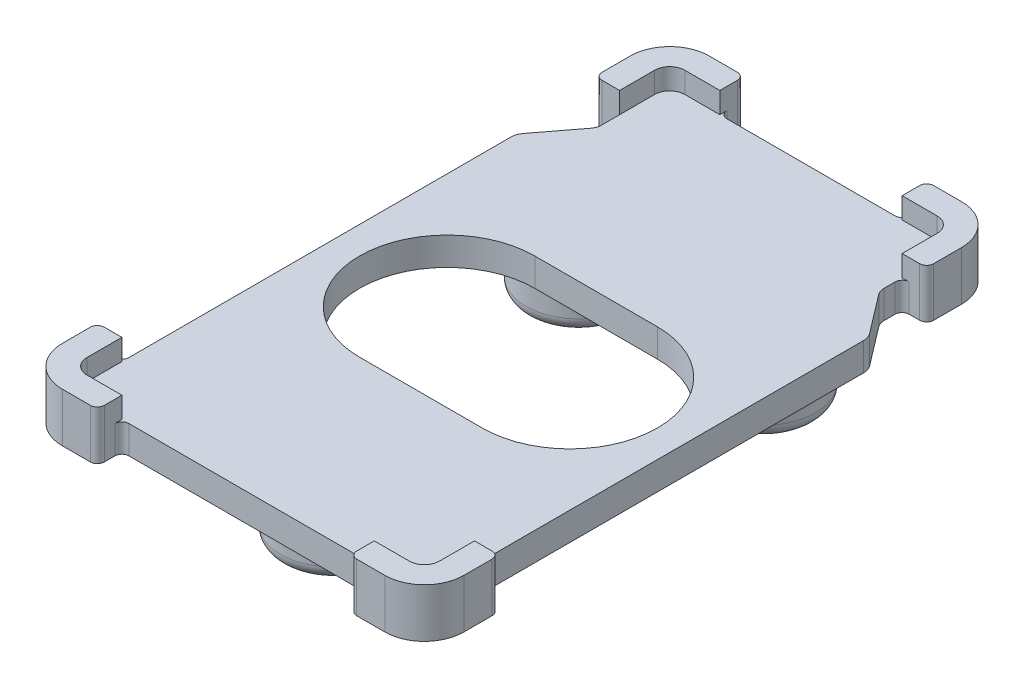
SolidWorks part; units mm, degrees
ref_plane "Alzado" through (0, 0, 0) normal (0, 0, 1) x (1, 0, 0)
ref_plane "Planta" through (0, 0, 0) normal (0, 1, 0) x (1, 0, 0)
ref_plane "Vista lateral" through (0, 0, 0) normal (1, 0, 0) x (0, 0, -1)
sketch "Croquis1" plane through (0, 0, 0) normal (0, 1, 0) x (1, 0, 0)
  line L0 (6, 80) -> (-6, 80) construction
  line L1 (6, 0) -> (-6, 0) construction
  line L2 (18, 80) -> (6, 80) construction
  line L3 (0, 80) -> (0, 0) construction
  line L4 (6, 0) -> (23, 0) construction
  line L5 (25, 2) -> (25, 62.5) construction
  line L6 (24.5908, 63.7121) -> (20.4092, 69.2003) construction
  line L7 (20, 70.4124) -> (20, 78) construction
  line L8 (-6, 0) -> (-23, 0) construction
  line L9 (-25, 2) -> (-25, 62.5) construction
  line L10 (-24.5908, 63.7121) -> (-20.4092, 69.2003) construction
  line L11 (-20, 70.4124) -> (-20, 78) construction
  line L12 (-18, 80) -> (-6, 80) construction
  line L13 (6, 80.15) -> (-6, 80.15)
  line L14 (-18, 80.15) -> (-6, 80.15)
  line L15 (-20.15, 70.4124) -> (-20.15, 78)
  line L16 (-24.7102, 63.803) -> (-20.5285, 69.2912)
  line L17 (-25.15, 2) -> (-25.15, 62.5)
  line L18 (-6, -0.15) -> (-23, -0.15)
  line L19 (6, -0.15) -> (-6, -0.15)
  line L20 (6, -0.15) -> (23, -0.15)
  line L21 (25.15, 2) -> (25.15, 62.5)
  line L22 (24.7102, 63.803) -> (20.5285, 69.2912)
  line L23 (20.15, 70.4124) -> (20.15, 78)
  line L24 (18, 80.15) -> (6, 80.15)
  arc A0 (23, 0) -> (25, 2) centre (23, 2) ccw construction
  arc A1 (25, 62.5) -> (24.5908, 63.7121) centre (23, 62.5) ccw construction
  arc A2 (20, 70.4124) -> (20.4092, 69.2003) centre (22, 70.4124) ccw construction
  arc A3 (20, 78) -> (18, 80) centre (18, 78) ccw construction
  arc A4 (-23, 0) -> (-25, 2) centre (-23, 2) cw construction
  arc A5 (-25, 62.5) -> (-24.5908, 63.7121) centre (-23, 62.5) cw construction
  arc A6 (-20, 70.4124) -> (-20.4092, 69.2003) centre (-22, 70.4124) cw construction
  arc A7 (-20, 78) -> (-18, 80) centre (-18, 78) cw construction
  arc A8 (-20.15, 78) -> (-18, 80.15) centre (-18, 78) cw
  arc A9 (-20.15, 70.4124) -> (-20.5285, 69.2912) centre (-22, 70.4124) cw
  arc A10 (-25.15, 62.5) -> (-24.7102, 63.803) centre (-23, 62.5) cw
  arc A11 (-23, -0.15) -> (-25.15, 2) centre (-23, 2) cw
  arc A12 (23, -0.15) -> (25.15, 2) centre (23, 2) ccw
  arc A13 (25.15, 62.5) -> (24.7102, 63.803) centre (23, 62.5) ccw
  arc A14 (20.15, 70.4124) -> (20.5285, 69.2912) centre (22, 70.4124) ccw
  arc A15 (20.15, 78) -> (18, 80.15) centre (18, 78) ccw
  dimension "D1" = 0.15
sketch "Croquis2" plane through (0, 0, 0) normal (0, 1, 0) x (1, 0, 0)
  line L0 (-24.7102, 63.803) -> (-20.5285, 69.2912) construction
  line L1 (-25.15, 2) -> (-25.15, 62.5) construction
  line L2 (-6, -0.15) -> (-23, -0.15) construction
  line L3 (6, -0.15) -> (-6, -0.15) construction
  line L4 (6, -0.15) -> (23, -0.15) construction
  line L5 (25.15, 2) -> (25.15, 62.5) construction
  line L6 (24.7102, 63.803) -> (20.5285, 69.2912) construction
  line L7 (20.15, 70.4124) -> (20.15, 78) construction
  line L8 (18, 80.15) -> (6, 80.15) construction
  line L9 (6, 80.15) -> (-6, 80.15) construction
  line L10 (-18, 80.15) -> (-6, 80.15) construction
  line L11 (-20.15, 70.4124) -> (-20.15, 78) construction
  line L12 (-24.7102, 63.803) -> (-20.5285, 69.2912)
  line L13 (-25.15, 2) -> (-25.15, 62.5)
  line L14 (-6, -0.15) -> (-23, -0.15)
  line L15 (6, -0.15) -> (-6, -0.15)
  line L16 (6, -0.15) -> (23, -0.15)
  line L17 (25.15, 2) -> (25.15, 62.5)
  line L18 (24.7102, 63.803) -> (20.5285, 69.2912)
  line L19 (20.15, 70.4124) -> (20.15, 78)
  line L20 (18, 80.15) -> (6, 80.15)
  line L21 (6, 80.15) -> (-6, 80.15)
  line L22 (-18, 80.15) -> (-6, 80.15)
  line L23 (-20.15, 70.4124) -> (-20.15, 78)
  line L24 (-27.4941, 65.9242) -> (-23.65, 70.9694)
  line L25 (-23.65, 70.9694) -> (-23.65, 78)
  line L26 (-18, 83.65) -> (-6, 83.65)
  line L27 (6, 83.65) -> (-6, 83.65)
  line L28 (18, 83.65) -> (6, 83.65)
  line L29 (23.65, 70.9694) -> (23.65, 78)
  line L30 (27.4941, 65.9242) -> (23.65, 70.9694)
  line L31 (28.65, 2) -> (28.65, 62.5)
  line L32 (6, -3.65) -> (23, -3.65)
  line L33 (6, -3.65) -> (-6, -3.65)
  line L34 (-6, -3.65) -> (-23, -3.65)
  line L35 (-28.65, 2) -> (-28.65, 62.5)
  line L36 (-23.65, 73) -> (-20.15, 73)
  line L37 (-13, 80.15) -> (-13, 83.65)
  line L38 (13, 83.65) -> (13, 80.15)
  line L39 (23.65, 73) -> (20.15, 73)
  line L40 (25.15, 7) -> (28.65, 7)
  line L41 (18, -0.15) -> (18, -3.65)
  line L42 (-18, -3.65) -> (-18, -0.15)
  line L43 (-25.15, 7) -> (-28.65, 7)
  arc A0 (-20.5285, 69.2912) -> (-20.15, 70.4124) centre (-22, 70.4124) ccw construction
  arc A1 (-24.7102, 63.803) -> (-25.15, 62.5) centre (-23, 62.5) ccw construction
  arc A2 (-25.15, 2) -> (-23, -0.15) centre (-23, 2) ccw construction
  arc A3 (23, -0.15) -> (25.15, 2) centre (23, 2) ccw construction
  arc A4 (25.15, 62.5) -> (24.7102, 63.803) centre (23, 62.5) ccw construction
  arc A5 (20.15, 70.4124) -> (20.5285, 69.2912) centre (22, 70.4124) ccw construction
  arc A6 (20.15, 78) -> (18, 80.15) centre (18, 78) ccw construction
  arc A7 (-18, 80.15) -> (-20.15, 78) centre (-18, 78) ccw construction
  arc A8 (-20.5285, 69.2912) -> (-20.15, 70.4124) centre (-22, 70.4124) ccw
  arc A9 (-24.7102, 63.803) -> (-25.15, 62.5) centre (-23, 62.5) ccw
  arc A10 (-25.15, 2) -> (-23, -0.15) centre (-23, 2) ccw
  arc A11 (23, -0.15) -> (25.15, 2) centre (23, 2) ccw
  arc A12 (25.15, 62.5) -> (24.7102, 63.803) centre (23, 62.5) ccw
  arc A13 (20.15, 70.4124) -> (20.5285, 69.2912) centre (22, 70.4124) ccw
  arc A14 (20.15, 78) -> (18, 80.15) centre (18, 78) ccw
  arc A15 (-18, 80.15) -> (-20.15, 78) centre (-18, 78) ccw
  arc A16 (-23.65, 70.9694) -> (-23.65, 70.9694) centre (-23.65, 70.9694) ccw
  arc A17 (-18, 83.65) -> (-23.65, 78) centre (-18, 78) ccw
  arc A18 (23.65, 78) -> (18, 83.65) centre (18, 78) ccw
  arc A19 (23.65, 70.9694) -> (23.65, 70.9694) centre (23.65, 70.9694) ccw
  arc A20 (28.65, 62.5) -> (27.4941, 65.9242) centre (23, 62.5) ccw
  arc A21 (23, -3.65) -> (28.65, 2) centre (23, 2) ccw
  arc A22 (-28.65, 2) -> (-23, -3.65) centre (-23, 2) ccw
  arc A23 (-27.4941, 65.9242) -> (-28.65, 62.5) centre (-23, 62.5) ccw
  dimension "D2" = 5
  dimension "D3" = 5
  dimension "D4" = 5
  dimension "D5" = 5
  dimension "D6" = 5
  dimension "D7" = 5
  dimension "D8" = 5
  dimension "D9" = 5
  dimension "D1" = 3.5
extrude "Saliente-Extruir1" add sketch "Croquis2" along normal blind 4 contours L22 A15 L23 A8 L12 A9 L13 A10 L14 L15 L16 A11 L17 A12 L18 A13 L19 A14 L20 L21 region at (0, 0, -38.8383)
extrude "Saliente-Extruir2" add sketch "Croquis2<3>" along normal blind 7 contours L35 A22 L34 L42 L14 A10 L13 L43 | L32 A21 L31 L40 L17 A11 L16 L41 | L29 A18 L28 L38 L20 A14 L19 L39 | L26 A17 L25 L36 L23 A15 L22 L37 region at (-25.3006, 0, -4.5) region at (-21.9, 0, -73.1506) region at (20.5, 0, 0.3006) region at (13.1506, 0, -81.9)
sketch "Croquis2<3>" plane through (0, 0, 0) normal (0, 1, 0) x (1, 0, 0) same geometry as "Croquis2"
fillet "Redondeo1" radius 1 15 edges at (23.65, 3.5, -73) (20.15, 2, -73) (13, 3.5, -83.65) (13, 2, -80.15) (18, 3.5, 3.65) (18, 2, 0.15) (25.15, 2, -7) (28.65, 3.5, -7) (-18, 3.5, 3.65) (-18, 2, 0.15) (-28.65, 3.5, -7) (-25.15, 2, -7) (-13, 3.5, -83.65) (-13, 2, -80.15) (-23.65, 3.5, -73)
sketch "Croquis3" plane through (0, 0, 0) normal (0, -1, 0) x (1, 0, 0)
  line L0 (-25.15, -8) -> (-25.15, -62.5) construction
  line L1 (-12, -80.15) -> (12, -80.15) construction
  circle A0 centre (0, -12) radius 7.5
  circle A1 centre (-13.15, -60.15) radius 7.5
  circle A2 centre (-13.15, -60.15) radius 3
  circle A3 centre (0, -12) radius 3
  dimension "D1" = 15
  dimension "D2" = 15
  dimension "D3" = 6
  dimension "D4" = 12
  dimension "D5" = 12
  dimension "D6" = 20
extrude "Saliente-Extruir3" add sketch "Croquis3" along normal blind 8 contours A0 A3 region at (-7.2879, 0, -12)
extrude "Saliente-Extruir4" add sketch "Croquis3<3>" along normal blind 8 contours A1 A2 region at (-20.4379, 0, -60.15)
sketch "Croquis3<3>" plane through (0, 0, 0) normal (0, -1, 0) x (1, 0, 0) same geometry as "Croquis3"
ref_plane "Plano1" through (0, 0, -12) normal (0, 0, 1) x (1, 0, 0)
sketch "Croquis4" plane through (0, 0, -12) normal (0, 0, 1) x (1, 0, 0)
  line L0 (5.125, -5.5) -> (-5.125, -5.5)
  line L1 (-7.5, -8) -> (7.5, -8) construction
  arc A0 (-5.125, -5.5) -> (5.125, -5.5) centre (0, -5.5) ccw
  dimension "D1" = 5.125
  dimension "D2" = 2.5
ref_plane "Plano2" through (0, 0, -60.15) normal (0, 0, 1) x (1, 0, 0)
sketch "Croquis5" plane through (0, 0, -60.15) normal (0, 0, 1) x (1, 0, 0)
  line L0 (-8.025, -5.5) -> (-18.275, -5.5)
  line L1 (-20.65, -8) -> (-5.65, -8) construction
  arc A0 (-18.275, -5.5) -> (-8.025, -5.5) centre (-13.15, -5.5) ccw
  dimension "D1" = 5.125
  dimension "D2" = 2.5
revolve "Cortar-Revolución1" cut sketch "Croquis4" angle 360 about L0
revolve "Cortar-Revolución2" cut sketch "Croquis5" angle 360 about L0
fillet "Redondeo2" radius 2 2 edges at (0, -8, -19.5) (0, 0, -4.5)
fillet "Redondeo3" radius 2 2 edges at (-13.15, -8, -67.65) (-13.15, 0, -52.65)
mirror "Simetría1" about plane through (0, 0, 0) normal (1, 0, 0) of "Redondeo3", "Cortar-Revolución2", "Saliente-Extruir4"
sketch "Croquis6" plane through (0, 0, 0) normal (0, -1, 0) x (1, 0, 0)
  line L0 (-8.75, -37) -> (8.75, -37) construction
  line L1 (-8.75, -24.5) -> (8.75, -24.5)
  line L2 (-8.75, -49.5) -> (8.75, -49.5)
  arc A0 (-8.75, -24.5) -> (-8.75, -49.5) centre (-8.75, -37) ccw
  arc A1 (8.75, -49.5) -> (8.75, -24.5) centre (8.75, -37) ccw
  point P2 (0, -37)
  dimension "D1" = 12.5
  dimension "D2" = 17.5
  dimension "D3" = 37
extrude "Cortar-Extruir1" cut sketch "Croquis6" against normal up to next
